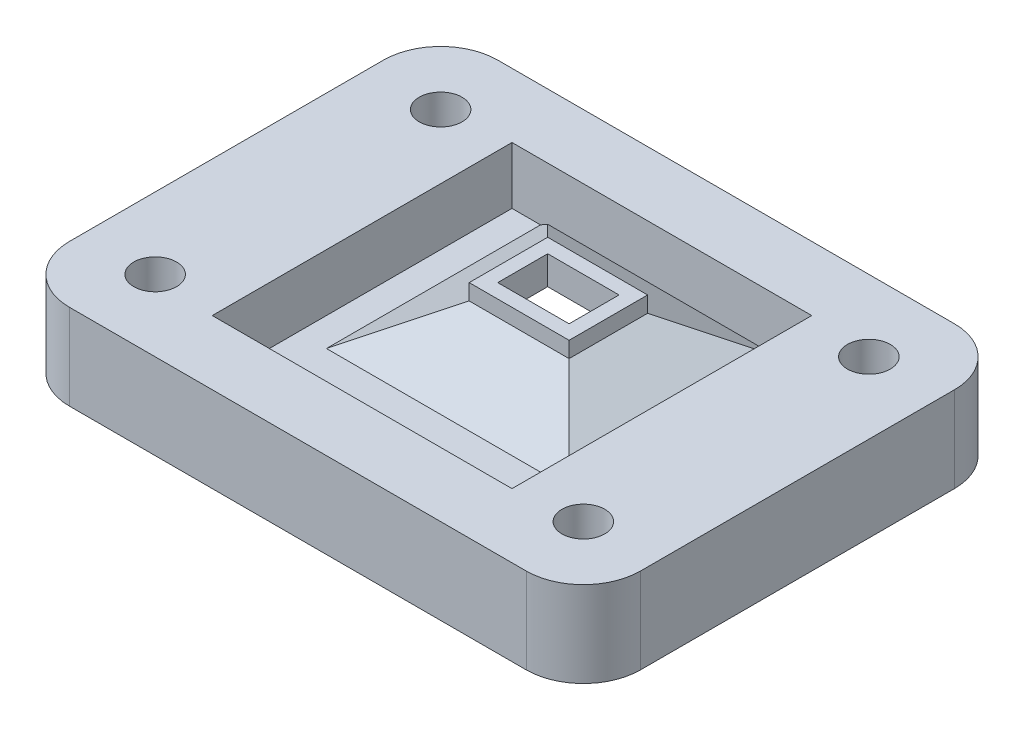
SolidWorks part; units mm, degrees
ref_plane "Front" through (0, 0, 0) normal (0, 0, 1) x (1, 0, 0)
ref_plane "Top" through (0, 0, 0) normal (0, 1, 0) x (1, 0, 0)
ref_plane "Right" through (0, 0, 0) normal (1, 0, 0) x (0, 0, -1)
sketch "Sketch1" plane through (0, 0, 0) normal (0, 1, 0) x (1, 0, 0)
  line L1 (0, 0) -> (40, 0)
  line L2 (0, 0) -> (0, 30)
  line L3 (0, 30) -> (40, 30)
  line L4 (40, 0) -> (40, 30)
  dimension "D1" = 40
  dimension "D2" = 30
extrude "Boss-Extrude1" add sketch "Sketch1" along normal blind 6
sketch "Sketch2" plane through (0, 6, 0) normal (0, 1, 0) x (1, 0, 0)
  line L0 (20, 30) -> (20, 0) construction
  line L1 (40, 30) -> (0, 30) construction
  line L2 (0, 0) -> (40, 0) construction
  line L3 (0, 15) -> (40, 15) construction
  line L4 (0, 30) -> (0, 0) construction
  line L5 (40, 0) -> (40, 30) construction
  circle A0 centre (5, 5) radius 1.5
  circle A1 centre (5, 25) radius 1.5
  circle A2 centre (35, 5) radius 1.5
  circle A3 centre (35, 25) radius 1.5
  dimension "D1" = 3
  dimension "D2" = 5
  dimension "D3" = 5
extrude "Cut-Extrude1" cut sketch "Sketch2" against normal up to surface (6 mm away) up to face at (20, 0, -15)
fillet "Fillet1" radius 4 4 edges at (0, 3, -30) (40, 3, -30) (40, 3, 0) (0, 3, 0)
sketch "Sketch3" plane through (0, 6, 0) normal (0, 1, 0) x (1, 0, 0)
  line L0 (4, 0) -> (36, 0) construction
  line L1 (9.5, 4.5) -> (30.5, 4.5)
  line L2 (9.5, 4.5) -> (9.5, 25.5)
  line L3 (9.5, 25.5) -> (30.5, 25.5)
  line L4 (30.5, 4.5) -> (30.5, 25.5)
  line L5 (0, 26) -> (0, 4) construction
  point P4 (20, 4.5)
  point P7 (20, 0)
  point P8 (9.5, 15)
  point P11 (0, 15)
  dimension "D1" = 21
  dimension "D2" = 21
extrude "Cut-Extrude2" cut sketch "Sketch3" against normal blind 4
sketch "Sketch6" plane through (0, 2, 0) normal (0, 1, 0) x (1, 0, 0)
  line L0 (9.5, 25.5) -> (9.5, 4.5) construction
  line L1 (17.5, 16.5) -> (22.5, 16.5)
  line L2 (17.5, 16.5) -> (17.5, 20)
  line L3 (17.5, 20) -> (22.5, 20)
  line L4 (22.5, 16.5) -> (22.5, 20)
  line L5 (30.5, 25.5) -> (9.5, 25.5) construction
  line L6 (30.5, 4.5) -> (30.5, 25.5) construction
  line L7 (9.5, 4.5) -> (30.5, 4.5) construction
  dimension "D1" = 8
  dimension "D2" = 8
  dimension "D3" = 12
  dimension "D4" = 5.5
extrude "Cut-Extrude3" cut sketch "Sketch6" against normal up to surface (2 mm away) up to face at (5, 0, -26.5)
sketch "Sketch7" plane through (0, 2, 0) normal (0, 1, 0) x (1, 0, 0)
  line L5 (17.5, 20) -> (22.5, 20)
  line L6 (17.5, 20) -> (17.5, 16.5)
  line L7 (17.5, 16.5) -> (22.5, 16.5)
  line L8 (16.5, 15.5) -> (23.5, 15.5)
  line L9 (23.5, 15.5) -> (23.5, 21)
  line L10 (23.5, 21) -> (16.5, 21)
  line L11 (16.5, 21) -> (16.5, 15.5)
  line L12 (16.5, 15.5) -> (23.5, 15.5)
  line L13 (23.5, 15.5) -> (23.5, 21)
  line L14 (23.5, 21) -> (16.5, 21)
  line L15 (16.5, 21) -> (16.5, 15.5)
  line L16 (22.5, 20) -> (22.5, 16.5)
  dimension "D1" = 1
extrude "Boss-Extrude2" add sketch "Sketch7" along normal blind 4
chamfer "Chamfer1" distance 4 angle 60 4 edges at (17.5, 0, -18.25) (20, 0, -16.5) (22.5, 0, -18.25) (20, 0, -20)
chamfer "Chamfer2" distance 5 angle 30 4 edges at (16.5, 2, -18.25) (20, 2, -21) (23.5, 2, -18.25) (20, 2, -15.5)
